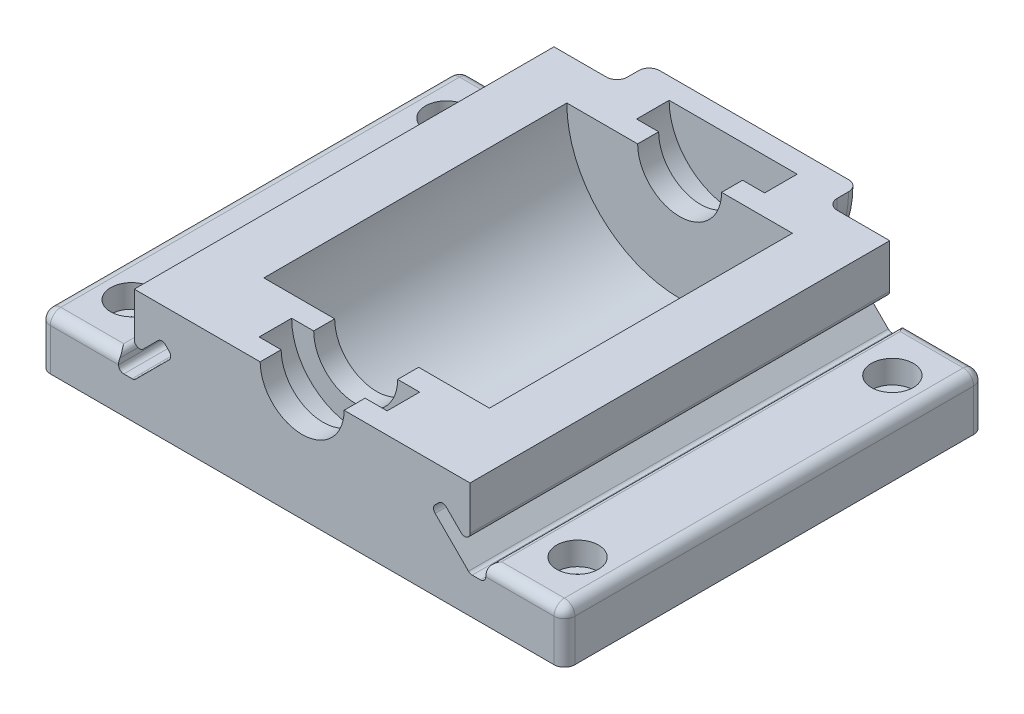
SolidWorks part; units mm, degrees
ref_plane "Plan de face" through (0, 0, 0) normal (0, 0, 1) x (1, 0, 0)
ref_plane "Plan de dessus" through (0, 0, 0) normal (0, 1, 0) x (1, 0, 0)
ref_plane "Plan de droite" through (0, 0, 0) normal (1, 0, 0) x (0, 0, -1)
sketch "Esquisse1" plane through (0, 0, 0) normal (0, 1, 0) x (1, 0, 0)
  line L1 (0, 0) -> (-100, 0)
  line L2 (0, 0) -> (0, 80)
  line L3 (0, 80) -> (-100, 80)
  line L4 (-100, 0) -> (-100, 80)
  dimension "D1" = 80
  dimension "D2" = 100
extrude "Boss.-Extru.1" add sketch "Esquisse1" along normal blind 10
sketch "Esquisse2" plane through (0, 10, 0) normal (0, 1, 0) x (1, 0, 0)
  line L0 (-85, 80) -> (-85, 0)
  line L1 (-15, 0) -> (-15, 80)
  line L4 (0, 0) -> (0, 80)
  line L5 (0, 80) -> (-100, 80)
  line L6 (-100, 80) -> (-100, 0)
  line L7 (-100, 0) -> (0, 0)
  line L8 (0, 0) -> (0, 80)
  line L9 (0, 80) -> (-100, 80)
  line L10 (-100, 80) -> (-100, 0)
  line L11 (-100, 0) -> (0, 0)
  line M6 (0, 80) -> (-100, 80)
  line M8 (-100, 0) -> (0, 0)
  dimension "D1" = 0
  dimension "D2" = 15
extrude "Boss.-Extru.2" add sketch "Esquisse2" along normal blind 12 contours L1 L0 M8 M6
sketch "Esquisse7" plane through (0, 0, -80) normal (0, 0, -1) x (-1, 0, 0)
  line L0 (15, 22) -> (85, 22) construction
  line L1 (15, 22) -> (85, 22)
  circle A0 centre (50, 22) radius 20
  dimension "D1" = 40
extrude "Boss.-Extru.3" add sketch "Esquisse7" along normal blind 6.15 contours L1 A0
sketch "Esquisse3" plane through (0, 22, 0) normal (0, 1, 0) x (1, 0, 0)
  line L0 (-50, 86.15) -> (-50, 0)
  line L2 (-85, 0) -> (-15, 0) construction
  line L3 (-70, 86.15) -> (-30, 86.15) construction
  line L4 (-50, 82.15) -> (-37.8, 82.15)
  line L5 (-50, 82.15) -> (-50, 75.95)
  line L6 (-50, 75.95) -> (-37.8, 75.95)
  line L7 (-37.8, 82.15) -> (-37.8, 75.95)
  line L8 (-50, 75.95) -> (-42, 75.95)
  line L9 (-50, 75.95) -> (-50, 71.95)
  line L10 (-50, 71.95) -> (-42, 71.95)
  line L11 (-42, 75.95) -> (-42, 71.95)
  line L12 (-50, 71.95) -> (-28.5, 71.95)
  line L13 (-50, 71.95) -> (-50, 14.2)
  line L14 (-50, 14.2) -> (-28.5, 14.2)
  line L15 (-28.5, 71.95) -> (-28.5, 14.2)
  line L16 (-50, 10.2) -> (-42, 10.2)
  line L17 (-50, 10.2) -> (-50, 14.2)
  line L18 (-50, 14.2) -> (-42, 14.2)
  line L19 (-42, 10.2) -> (-42, 14.2)
  line L20 (-50, 4) -> (-37.8, 4)
  line L21 (-50, 4) -> (-50, 10.2)
  line L22 (-50, 10.2) -> (-37.8, 10.2)
  line L23 (-37.8, 4) -> (-37.8, 10.2)
  line L24 (-50, 0) -> (-42, 0)
  line L25 (-50, 0) -> (-50, 4)
  line L26 (-50, 4) -> (-42, 4)
  line L27 (-42, 0) -> (-42, 4)
  line L28 (-70, 86.15) -> (-30, 86.15)
  point P33 (-50, 86.15)
  dimension "D2" = 6.2
  dimension "D3" = 12.2
  dimension "D4" = 4
  dimension "D5" = 8
  dimension "D6" = 4
  dimension "D7" = 4
  dimension "D8" = 8
  dimension "D9" = 6.2
  dimension "D10" = 12.2
  dimension "D11" = 8
  dimension "D12" = 21.5
  dimension "D13" = 4
revolve "Enlèvement de matière-Révolution1" cut sketch "Esquisse3" angle 360 about L0
sketch "Esquisse4" plane through (0, 10, 0) normal (0, 1, 0) x (1, 0, 0)
  line L0 (-92.5, 80) -> (-92.5, 0)
  line L1 (-85, 80) -> (-100, 80) construction
  line L2 (-100, 0) -> (-85, 0) construction
  line L3 (-7.5, 80) -> (-7.5, 0)
  line L4 (0, 80) -> (-15, 80) construction
  line L5 (-15, 0) -> (0, 0) construction
  point P12 (-92.5, 70)
  point P13 (-92.5, 10)
  point P14 (-7.5, 70)
  point P15 (-7.5, 10)
  dimension "D1" = 10
  dimension "D2" = 10
  dimension "D3" = 10
  dimension "D4" = 10
hole_wizard "Chambrage pour vis à six pans creux M41" positions "Esquisse3D1" profile "Esquisse5" counterbore size "M4" standard "ISO" end condition through all
sketch3d "Esquisse3D1"
  point P0 (-92.5, 10, -70)
  point P3 (-92.5, 10, -10)
  point P6 (-7.5, 10, -10)
  point P9 (-7.5, 10, -70)
sketch "Esquisse5" plane through (-92.5, 10, -70) normal (1, 0, 0) x (0, 0, 1)
  line L0 (0, 0) -> (0, 10)
  line L1 (0, 10) -> (2.25, 10)
  line L3 (2.25, 10) -> (2.25, 4.4)
  line L4 (2.25, 4.4) -> (4, 4.4)
  line L5 (4, 4.4) -> (4, 0)
  line L7 (4, 0) -> (0, 0)
  line L11 (0, -6.35) -> (0, 107.95) construction
  dimension "Diamètre du perçage jusqu'au prochain" = 4.5
  dimension "Profondeur du perçage jusqu'au prochain" = 10
  dimension "Diamètre du chambrage" = 8
  dimension "Profondeur du chambrage" = 4.4
sketch "Esquisse6" plane through (0, 0, 0) normal (0, 0, 1) x (1, 0, 0)
  line L0 (-50, 22) -> (-50, 0)
  line L1 (-81.7071, 7.2929) -> (-75.3431, 13.6569)
  line L2 (-85, 22) -> (-82, 22)
  line L3 (-85, 9) -> (-85, 8)
  line L4 (-84, 7) -> (-82.4142, 7)
  line L5 (-82, 22) -> (-82, 13.6569)
  line L6 (-81.7071, 7.2929) -> (-74.636, 14.364)
  line L8 (-75.3431, 15.0711) -> (-76.0503, 15.7782)
  line L9 (-58, 22) -> (-85, 22)
  line L10 (-85, 22) -> (-85, 10)
  line L11 (-85, 10) -> (-100, 10)
  line L12 (-100, 10) -> (-100, 0)
  line L13 (-100, 0) -> (0, 0)
  line L14 (0, 0) -> (0, 10)
  line L15 (0, 10) -> (-15, 10)
  line L16 (-15, 10) -> (-15, 22)
  line L17 (-15, 22) -> (-42, 22)
  line L18 (-58, 22) -> (-85, 22)
  line L19 (-85, 22) -> (-85, 10)
  line L20 (-86, 10) -> (-100, 10)
  line L21 (-100, 10) -> (-100, 0)
  line L22 (-100, 0) -> (0, 0)
  line L23 (0, 0) -> (0, 10)
  line L24 (0, 10) -> (-15, 10)
  line L25 (-15, 10) -> (-15, 22)
  line L26 (-15, 22) -> (-42, 22)
  line L27 (-80.2929, 12.9497) -> (-77.4645, 15.7782)
  line L28 (-18, 22) -> (-18, 13.6569)
  line L29 (-19.7071, 12.9497) -> (-22.5355, 15.7782)
  line L30 (-24.6569, 15.0711) -> (-23.9497, 15.7782)
  line L31 (-18.2929, 7.2929) -> (-24.6569, 13.6569)
  line L32 (-16, 7) -> (-17.5858, 7)
  line L33 (-15, 9) -> (-15, 8)
  arc A0 (-85, 9) -> (-86, 10) centre (-86, 9) ccw
  arc A1 (-58, 22) -> (-42, 22) centre (-50, 22) ccw
  arc A2 (-58, 22) -> (-42, 22) centre (-50, 22) ccw
  arc A3 (-84, 7) -> (-85, 8) centre (-84, 8) cw
  arc A4 (-82.4142, 7) -> (-81.7071, 7.2929) centre (-82.4142, 8) ccw
  arc A5 (-75.3431, 13.6569) -> (-75.3431, 15.0711) centre (-76.0503, 14.364) ccw
  arc A6 (-76.0503, 15.7782) -> (-77.4645, 15.7782) centre (-76.7574, 15.0711) ccw
  arc A7 (-80.2929, 12.9497) -> (-82, 13.6569) centre (-81, 13.6569) cw
  arc A8 (-19.7071, 12.9497) -> (-18, 13.6569) centre (-19, 13.6569) ccw
  arc A9 (-23.9497, 15.7782) -> (-22.5355, 15.7782) centre (-23.2426, 15.0711) cw
  arc A10 (-24.6569, 13.6569) -> (-24.6569, 15.0711) centre (-23.9497, 14.364) cw
  arc A11 (-17.5858, 7) -> (-18.2929, 7.2929) centre (-17.5858, 8) cw
  arc A12 (-16, 7) -> (-15, 8) centre (-16, 8) ccw
  arc A13 (-15, 9) -> (-14, 10) centre (-14, 9) cw
  point P31 (-76.7574, 16.4853)
  line M20 (-58, 22) -> (-85, 22)
  line M21 (-85, 22) -> (-85, 10)
  line M22 (-85, 10) -> (-100, 10)
  line M27 (-15, 10) -> (-15, 22)
  line M28 (-15, 22) -> (-42, 22)
  dimension "D3" = 1
  dimension "D7" = 1
  dimension "D8" = 1
  dimension "D9" = 1
  dimension "D10" = 1
  dimension "D4" = 1
  dimension "D2" = 15
  dimension "D5" = 45
  dimension "D6" = 3
  dimension "D11" = 3
  dimension "D12" = 9
  dimension "D13" = 3
  dimension "D14" = 4
  dimension "D1" = 0
extrude "Enlèv. mat.-Extru.1" cut sketch "Esquisse6" against normal through all contours L33 A13 L24 L28 A8 L29 A9 L30 A10 L31 A11 L32 A12 M27 M28 | L27 A7 L5 A0 L3 A3 L4 A4 L1 A5 L8 A6 M20 M21 M22
fillet "Congé1" radius 2 12 edges at (0, 5, -80) (-100, 5, -80) (0, 5, 0) (-100, 5, 0) (0, 10, -40) (-7, 10, 0) (-100, 10, -40) (-93, 10, 0) (-7, 10, -80) (-50, 2, -86.15) (-50, 2, -80) (-93, 10, -80)
